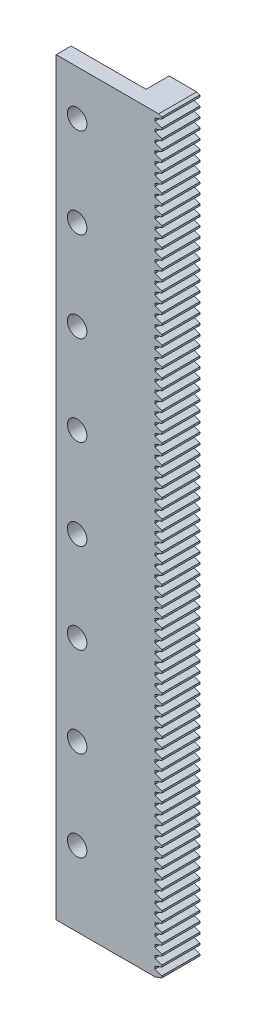
SolidWorks part; units mm, degrees
ref_plane "Front Plane" through (0, 0, 0) normal (0, 0, 1) x (1, 0, 0)
ref_plane "Top Plane" through (0, 0, 0) normal (0, 1, 0) x (1, 0, 0)
ref_plane "Right Plane" through (0, 0, 0) normal (1, 0, 0) x (0, 0, -1)
sketch "Sketch2" plane through (0, 0, 0) normal (0, 0, 1) x (1, 0, 0)
  line L0 (0, -62.5) -> (0, 62.5) construction
  line L1 (-3.5, -62.5) -> (3.5, -62.5) construction
  line L2 (-3.5, -62.5) -> (-3.5, 62.5) construction
  line L3 (-3.5, 62.5) -> (3.5, 62.5) construction
  line L4 (3.5, -62.5) -> (3.5, 62.5) construction
  line L5 (-3.5, -62.5) -> (3.5, 62.5) construction
  line L6 (-3.5, 62.5) -> (3.5, -62.5) construction
  line L202 (3.5, -62.5) -> (-3.5, -62.5)
  line L203 (-3.5, -62.5) -> (-3.5, 62.5)
  line L204 (-3.5, 62.5) -> (13.6024, 62.5)
  line L591 (3.5, -62.5) -> (8, -62.5)
  line L592 (-8, -15) -> (8, -15) construction
  line L593 (-8, -15) -> (-8, 15) construction
  line L594 (-8, 15) -> (8, 15) construction
  line L595 (8, -15) -> (8, 15) construction
  line L596 (-8, -15) -> (8, 15) construction
  line L597 (-8, 15) -> (8, -15) construction
  line L598 (8, -62.5) -> (13, -62.5)
  line L600 (13, -62.5) -> (14.125, -62.0905)
  line L601 (14.125, -62.0905) -> (14.125, -61.7831)
  line L602 (14.125, -61.7831) -> (13, -61.3736)
  line L603 (13, -61.3736) -> (13, -60.9292)
  line L604 (13, -60.9292) -> (14.125, -60.5197)
  line L605 (14.125, -60.5197) -> (14.125, -60.2123)
  line L606 (14.125, -60.2123) -> (13, -59.8028)
  line L607 (13, -59.8028) -> (13, -59.3584)
  line L608 (13, -59.3584) -> (14.125, -58.9489)
  line L609 (14.125, -58.9489) -> (14.125, -58.6415)
  line L610 (14.125, -58.6415) -> (13, -58.232)
  line L611 (13, -58.232) -> (13, -57.7876)
  line L612 (13, -57.7876) -> (14.125, -57.3781)
  line L613 (14.125, -57.3781) -> (14.125, -57.0707)
  line L614 (14.125, -57.0707) -> (13, -56.6613)
  line L615 (13, -56.6613) -> (13, -56.2168)
  line L616 (13, -56.2168) -> (14.125, -55.8073)
  line L617 (14.125, -55.8073) -> (14.125, -55.4999)
  line L618 (14.125, -55.4999) -> (13, -55.0905)
  line L619 (13, -55.0905) -> (13, -54.646)
  line L620 (13, -54.646) -> (14.125, -54.2366)
  line L621 (14.125, -54.2366) -> (14.125, -53.9291)
  line L622 (14.125, -53.9291) -> (13, -53.5197)
  line L623 (13, -53.5197) -> (13, -53.0752)
  line L624 (13, -53.0752) -> (14.125, -52.6658)
  line L625 (14.125, -52.6658) -> (14.125, -52.3583)
  line L626 (14.125, -52.3583) -> (13, -51.9489)
  line L627 (13, -51.9489) -> (13, -51.5044)
  line L628 (13, -51.5044) -> (14.125, -51.095)
  line L629 (14.125, -51.095) -> (14.125, -50.7875)
  line L630 (14.125, -50.7875) -> (13, -50.3781)
  line L631 (13, -50.3781) -> (13, -49.9336)
  line L632 (13, -49.9336) -> (14.125, -49.5242)
  line L633 (14.125, -49.5242) -> (14.125, -49.2167)
  line L634 (14.125, -49.2167) -> (13, -48.8073)
  line L635 (13, -48.8073) -> (13, -48.3628)
  line L636 (13, -48.3628) -> (14.125, -47.9534)
  line L637 (14.125, -47.9534) -> (14.125, -47.6459)
  line L638 (14.125, -47.6459) -> (13, -47.2365)
  line L639 (13, -47.2365) -> (13, -46.792)
  line L640 (13, -46.792) -> (14.125, -46.3826)
  line L641 (14.125, -46.3826) -> (14.125, -46.0751)
  line L642 (14.125, -46.0751) -> (13, -45.6657)
  line L643 (13, -45.6657) -> (13, -45.2212)
  line L644 (13, -45.2212) -> (14.125, -44.8118)
  line L645 (14.125, -44.8118) -> (14.125, -44.5043)
  line L646 (14.125, -44.5043) -> (13, -44.0949)
  line L647 (13, -44.0949) -> (13, -43.6504)
  line L648 (13, -43.6504) -> (14.125, -43.241)
  line L649 (14.125, -43.241) -> (14.125, -42.9335)
  line L650 (14.125, -42.9335) -> (13, -42.5241)
  line L651 (13, -42.5241) -> (13, -42.0796)
  line L652 (13, -42.0796) -> (14.125, -41.6702)
  line L653 (14.125, -41.6702) -> (14.125, -41.3628)
  line L654 (14.125, -41.3628) -> (13, -40.9533)
  line L655 (13, -40.9533) -> (13, -40.5089)
  line L656 (13, -40.5089) -> (14.125, -40.0994)
  line L657 (14.125, -40.0994) -> (14.125, -39.792)
  line L658 (14.125, -39.792) -> (13, -39.3825)
  line L659 (13, -39.3825) -> (13, -38.9381)
  line L660 (13, -38.9381) -> (14.125, -38.5286)
  line L661 (14.125, -38.5286) -> (14.125, -38.2212)
  line L662 (14.125, -38.2212) -> (13, -37.8117)
  line L663 (13, -37.8117) -> (13, -37.3673)
  line L664 (13, -37.3673) -> (14.125, -36.9578)
  line L665 (14.125, -36.9578) -> (14.125, -36.6504)
  line L666 (14.125, -36.6504) -> (13, -36.2409)
  line L667 (13, -36.2409) -> (13, -35.7965)
  line L668 (13, -35.7965) -> (14.125, -35.387)
  line L669 (14.125, -35.387) -> (14.125, -35.0796)
  line L670 (14.125, -35.0796) -> (13, -34.6701)
  line L671 (13, -34.6701) -> (13, -34.2257)
  line L672 (13, -34.2257) -> (14.125, -33.8162)
  line L673 (14.125, -33.8162) -> (14.125, -33.5088)
  line L674 (14.125, -33.5088) -> (13, -33.0993)
  line L675 (13, -33.0993) -> (13, -32.6549)
  line L676 (13, -32.6549) -> (14.125, -32.2454)
  line L677 (14.125, -32.2454) -> (14.125, -31.938)
  line L678 (14.125, -31.938) -> (13, -31.5285)
  line L679 (13, -31.5285) -> (13, -31.0841)
  line L680 (13, -31.0841) -> (14.125, -30.6746)
  line L681 (14.125, -30.6746) -> (14.125, -30.3672)
  line L682 (14.125, -30.3672) -> (13, -29.9577)
  line L683 (13, -29.9577) -> (13, -29.5133)
  line L684 (13, -29.5133) -> (14.125, -29.1038)
  line L685 (14.125, -29.1038) -> (14.125, -28.7964)
  line L686 (14.125, -28.7964) -> (13, -28.3869)
  line L687 (13, -28.3869) -> (13, -27.9425)
  line L688 (13, -27.9425) -> (14.125, -27.533)
  line L689 (14.125, -27.533) -> (14.125, -27.2256)
  line L690 (14.125, -27.2256) -> (13, -26.8161)
  line L691 (13, -26.8161) -> (13, -26.3717)
  line L692 (13, -26.3717) -> (14.125, -25.9622)
  line L693 (14.125, -25.9622) -> (14.125, -25.6548)
  line L694 (14.125, -25.6548) -> (13, -25.2453)
  line L695 (13, -25.2453) -> (13, -24.8009)
  line L696 (13, -24.8009) -> (14.125, -24.3914)
  line L697 (14.125, -24.3914) -> (14.125, -24.084)
  line L698 (14.125, -24.084) -> (13, -23.6745)
  line L699 (13, -23.6745) -> (13, -23.2301)
  line L700 (13, -23.2301) -> (14.125, -22.8206)
  line L701 (14.125, -22.8206) -> (14.125, -22.5132)
  line L702 (14.125, -22.5132) -> (13, -22.1037)
  line L703 (13, -22.1037) -> (13, -21.6593)
  line L704 (13, -21.6593) -> (14.125, -21.2498)
  line L705 (14.125, -21.2498) -> (14.125, -20.9424)
  line L706 (14.125, -20.9424) -> (13, -20.5329)
  line L707 (13, -20.5329) -> (13, -20.0885)
  line L708 (13, -20.0885) -> (14.125, -19.679)
  line L709 (14.125, -19.679) -> (14.125, -19.3716)
  line L710 (14.125, -19.3716) -> (13, -18.9621)
  line L711 (13, -18.9621) -> (13, -18.5177)
  line L712 (13, -18.5177) -> (14.125, -18.1082)
  line L713 (14.125, -18.1082) -> (14.125, -17.8008)
  line L714 (14.125, -17.8008) -> (13, -17.3913)
  line L715 (13, -17.3913) -> (13, -16.9469)
  line L716 (13, -16.9469) -> (14.125, -16.5374)
  line L717 (14.125, -16.5374) -> (14.125, -16.23)
  line L718 (14.125, -16.23) -> (13, -15.8205)
  line L719 (13, -15.8205) -> (13, -15.3761)
  line L720 (13, -15.3761) -> (14.125, -14.9666)
  line L721 (14.125, -14.9666) -> (14.125, -14.6592)
  line L722 (14.125, -14.6592) -> (13, -14.2497)
  line L723 (13, -14.2497) -> (13, -13.8053)
  line L724 (13, -13.8053) -> (14.125, -13.3958)
  line L725 (14.125, -13.3958) -> (14.125, -13.0884)
  line L726 (14.125, -13.0884) -> (13, -12.679)
  line L727 (13, -12.679) -> (13, -12.2345)
  line L728 (13, -12.2345) -> (14.125, -11.8251)
  line L729 (14.125, -11.8251) -> (14.125, -11.5176)
  line L730 (14.125, -11.5176) -> (13, -11.1082)
  line L731 (13, -11.1082) -> (13, -10.6637)
  line L732 (13, -10.6637) -> (14.125, -10.2543)
  line L733 (14.125, -10.2543) -> (14.125, -9.9468)
  line L734 (14.125, -9.9468) -> (13, -9.5374)
  line L735 (13, -9.5374) -> (13, -9.0929)
  line L736 (13, -9.0929) -> (14.125, -8.6835)
  line L737 (14.125, -8.6835) -> (14.125, -8.376)
  line L738 (14.125, -8.376) -> (13, -7.9666)
  line L739 (13, -7.9666) -> (13, -7.5221)
  line L740 (13, -7.5221) -> (14.125, -7.1127)
  line L741 (14.125, -7.1127) -> (14.125, -6.8052)
  line L742 (14.125, -6.8052) -> (13, -6.3958)
  line L743 (13, -6.3958) -> (13, -5.9513)
  line L744 (13, -5.9513) -> (14.125, -5.5419)
  line L745 (14.125, -5.5419) -> (14.125, -5.2344)
  line L746 (14.125, -5.2344) -> (13, -4.825)
  line L747 (13, -4.825) -> (13, -4.3805)
  line L748 (13, -4.3805) -> (14.125, -3.9711)
  line L749 (14.125, -3.9711) -> (14.125, -3.6636)
  line L750 (14.125, -3.6636) -> (13, -3.2542)
  line L751 (13, -3.2542) -> (13, -2.8097)
  line L752 (13, -2.8097) -> (14.125, -2.4003)
  line L753 (14.125, -2.4003) -> (14.125, -2.0928)
  line L754 (14.125, -2.0928) -> (13, -1.6834)
  line L755 (13, -1.6834) -> (13, -1.2389)
  line L756 (13, -1.2389) -> (14.125, -0.8295)
  line L757 (14.125, -0.8295) -> (14.125, -0.522)
  line L758 (14.125, -0.522) -> (13, -0.1126)
  line L759 (13, -0.1126) -> (13, 0.3319)
  line L760 (13, 0.3319) -> (14.125, 0.7413)
  line L761 (14.125, 0.7413) -> (14.125, 1.0487)
  line L762 (14.125, 1.0487) -> (13, 1.4582)
  line L763 (13, 1.4582) -> (13, 1.9026)
  line L764 (13, 1.9026) -> (14.125, 2.3121)
  line L765 (14.125, 2.3121) -> (14.125, 2.6195)
  line L766 (14.125, 2.6195) -> (13, 3.029)
  line L767 (13, 3.029) -> (13, 3.4734)
  line L768 (13, 3.4734) -> (14.125, 3.8829)
  line L769 (14.125, 3.8829) -> (14.125, 4.1903)
  line L770 (14.125, 4.1903) -> (13, 4.5998)
  line L771 (13, 4.5998) -> (13, 5.0442)
  line L772 (13, 5.0442) -> (14.125, 5.4537)
  line L773 (14.125, 5.4537) -> (14.125, 5.7611)
  line L774 (14.125, 5.7611) -> (13, 6.1706)
  line L775 (13, 6.1706) -> (13, 6.615)
  line L776 (13, 6.615) -> (14.125, 7.0245)
  line L777 (14.125, 7.0245) -> (14.125, 7.3319)
  line L778 (14.125, 7.3319) -> (13, 7.7414)
  line L779 (13, 7.7414) -> (13, 8.1858)
  line L780 (13, 8.1858) -> (14.125, 8.5953)
  line L781 (14.125, 8.5953) -> (14.125, 8.9027)
  line L782 (14.125, 8.9027) -> (13, 9.3122)
  line L783 (13, 9.3122) -> (13, 9.7566)
  line L784 (13, 9.7566) -> (14.125, 10.1661)
  line L785 (14.125, 10.1661) -> (14.125, 10.4735)
  line L786 (14.125, 10.4735) -> (13, 10.883)
  line L787 (13, 10.883) -> (13, 11.3274)
  line L788 (13, 11.3274) -> (14.125, 11.7369)
  line L789 (14.125, 11.7369) -> (14.125, 12.0443)
  line L790 (14.125, 12.0443) -> (13, 12.4538)
  line L791 (13, 12.4538) -> (13, 12.8982)
  line L792 (13, 12.8982) -> (14.125, 13.3077)
  line L793 (14.125, 13.3077) -> (14.125, 13.6151)
  line L794 (14.125, 13.6151) -> (13, 14.0246)
  line L795 (13, 14.0246) -> (13, 14.469)
  line L796 (13, 14.469) -> (14.125, 14.8785)
  line L797 (14.125, 14.8785) -> (14.125, 15.1859)
  line L798 (14.125, 15.1859) -> (13, 15.5954)
  line L799 (13, 15.5954) -> (13, 16.0398)
  line L800 (13, 16.0398) -> (14.125, 16.4493)
  line L801 (14.125, 16.4493) -> (14.125, 16.7567)
  line L802 (14.125, 16.7567) -> (13, 17.1662)
  line L803 (13, 17.1662) -> (13, 17.6106)
  line L804 (13, 17.6106) -> (14.125, 18.0201)
  line L805 (14.125, 18.0201) -> (14.125, 18.3275)
  line L806 (14.125, 18.3275) -> (13, 18.737)
  line L807 (13, 18.737) -> (13, 19.1814)
  line L808 (13, 19.1814) -> (14.125, 19.5909)
  line L809 (14.125, 19.5909) -> (14.125, 19.8983)
  line L810 (14.125, 19.8983) -> (13, 20.3078)
  line L811 (13, 20.3078) -> (13, 20.7522)
  line L812 (13, 20.7522) -> (14.125, 21.1617)
  line L813 (14.125, 21.1617) -> (14.125, 21.4691)
  line L814 (14.125, 21.4691) -> (13, 21.8786)
  line L815 (13, 21.8786) -> (13, 22.323)
  line L816 (13, 22.323) -> (14.125, 22.7325)
  line L817 (14.125, 22.7325) -> (14.125, 23.0399)
  line L818 (14.125, 23.0399) -> (13, 23.4494)
  line L819 (13, 23.4494) -> (13, 23.8938)
  line L820 (13, 23.8938) -> (14.125, 24.3033)
  line L821 (14.125, 24.3033) -> (14.125, 24.6107)
  line L822 (14.125, 24.6107) -> (13, 25.0202)
  line L823 (13, 25.0202) -> (13, 25.4646)
  line L824 (13, 25.4646) -> (14.125, 25.8741)
  line L825 (14.125, 25.8741) -> (14.125, 26.1815)
  line L826 (14.125, 26.1815) -> (13, 26.591)
  line L827 (13, 26.591) -> (13, 27.0354)
  line L828 (13, 27.0354) -> (14.125, 27.4449)
  line L829 (14.125, 27.4449) -> (14.125, 27.7523)
  line L830 (14.125, 27.7523) -> (13, 28.1618)
  line L831 (13, 28.1618) -> (13, 28.6062)
  line L832 (13, 28.6062) -> (14.125, 29.0157)
  line L833 (14.125, 29.0157) -> (14.125, 29.3231)
  line L834 (14.125, 29.3231) -> (13, 29.7325)
  line L835 (13, 29.7325) -> (13, 30.177)
  line L836 (13, 30.177) -> (14.125, 30.5864)
  line L837 (14.125, 30.5864) -> (14.125, 30.8939)
  line L838 (14.125, 30.8939) -> (13, 31.3033)
  line L839 (13, 31.3033) -> (13, 31.7478)
  line L840 (13, 31.7478) -> (14.125, 32.1572)
  line L841 (14.125, 32.1572) -> (14.125, 32.4647)
  line L842 (14.125, 32.4647) -> (13, 32.8741)
  line L843 (13, 32.8741) -> (13, 33.3186)
  line L844 (13, 33.3186) -> (14.125, 33.728)
  line L845 (14.125, 33.728) -> (14.125, 34.0355)
  line L846 (14.125, 34.0355) -> (13, 34.4449)
  line L847 (13, 34.4449) -> (13, 34.8894)
  line L848 (13, 34.8894) -> (14.125, 35.2988)
  line L849 (14.125, 35.2988) -> (14.125, 35.6063)
  line L850 (14.125, 35.6063) -> (13, 36.0157)
  line L851 (13, 36.0157) -> (13, 36.4602)
  line L852 (13, 36.4602) -> (14.125, 36.8696)
  line L853 (14.125, 36.8696) -> (14.125, 37.1771)
  line L854 (14.125, 37.1771) -> (13, 37.5865)
  line L855 (13, 37.5865) -> (13, 38.031)
  line L856 (13, 38.031) -> (14.125, 38.4404)
  line L857 (14.125, 38.4404) -> (14.125, 38.7479)
  line L858 (14.125, 38.7479) -> (13, 39.1573)
  line L859 (13, 39.1573) -> (13, 39.6018)
  line L860 (13, 39.6018) -> (14.125, 40.0112)
  line L861 (14.125, 40.0112) -> (14.125, 40.3187)
  line L862 (14.125, 40.3187) -> (13, 40.7281)
  line L863 (13, 40.7281) -> (13, 41.1726)
  line L864 (13, 41.1726) -> (14.125, 41.582)
  line L865 (14.125, 41.582) -> (14.125, 41.8895)
  line L866 (14.125, 41.8895) -> (13, 42.2989)
  line L867 (13, 42.2989) -> (13, 42.7434)
  line L868 (13, 42.7434) -> (14.125, 43.1528)
  line L869 (14.125, 43.1528) -> (14.125, 43.4602)
  line L870 (14.125, 43.4602) -> (13, 43.8697)
  line L871 (13, 43.8697) -> (13, 44.3142)
  line L872 (13, 44.3142) -> (14.125, 44.7236)
  line L873 (14.125, 44.7236) -> (14.125, 45.031)
  line L874 (14.125, 45.031) -> (13, 45.4405)
  line L875 (13, 45.4405) -> (13, 45.8849)
  line L876 (13, 45.8849) -> (14.125, 46.2944)
  line L877 (14.125, 46.2944) -> (14.125, 46.6018)
  line L878 (14.125, 46.6018) -> (13, 47.0113)
  line L879 (13, 47.0113) -> (13, 47.4557)
  line L880 (13, 47.4557) -> (14.125, 47.8652)
  line L881 (14.125, 47.8652) -> (14.125, 48.1726)
  line L882 (14.125, 48.1726) -> (13, 48.5821)
  line L883 (13, 48.5821) -> (13, 49.0265)
  line L884 (13, 49.0265) -> (14.125, 49.436)
  line L885 (14.125, 49.436) -> (14.125, 49.7434)
  line L886 (14.125, 49.7434) -> (13, 50.1529)
  line L887 (13, 50.1529) -> (13, 50.5973)
  line L888 (13, 50.5973) -> (14.125, 51.0068)
  line L889 (14.125, 51.0068) -> (14.125, 51.3142)
  line L890 (14.125, 51.3142) -> (13, 51.7237)
  line L891 (13, 51.7237) -> (13, 52.1681)
  line L892 (13, 52.1681) -> (14.125, 52.5776)
  line L893 (14.125, 52.5776) -> (14.125, 52.885)
  line L894 (14.125, 52.885) -> (13, 53.2945)
  line L895 (13, 53.2945) -> (13, 53.7389)
  line L896 (13, 53.7389) -> (14.125, 54.1484)
  line L897 (14.125, 54.1484) -> (14.125, 54.4558)
  line L898 (14.125, 54.4558) -> (13, 54.8653)
  line L899 (13, 54.8653) -> (13, 55.3097)
  line L900 (13, 55.3097) -> (14.125, 55.7192)
  line L901 (14.125, 55.7192) -> (14.125, 56.0266)
  line L902 (14.125, 56.0266) -> (13, 56.4361)
  line L903 (13, 56.4361) -> (13, 56.8805)
  line L904 (13, 56.8805) -> (14.125, 57.29)
  line L905 (14.125, 57.29) -> (14.125, 57.5974)
  line L906 (14.125, 57.5974) -> (13, 58.0069)
  line L907 (13, 58.0069) -> (13, 58.4513)
  line L908 (13, 58.4513) -> (14.125, 58.8608)
  line L909 (14.125, 58.8608) -> (14.125, 59.1682)
  line L910 (14.125, 59.1682) -> (13, 59.5777)
  line L911 (13, 59.5777) -> (13, 60.0221)
  line L912 (13, 60.0221) -> (14.125, 60.4316)
  line L913 (14.125, 60.4316) -> (14.125, 60.739)
  line L914 (14.125, 60.739) -> (13, 61.1485)
  line L915 (13, 61.1485) -> (13, 61.5929)
  line L916 (13, 61.5929) -> (14.125, 62.0024)
  line L917 (14.125, 62.0024) -> (14.125, 62.3098)
  line L918 (14.125, 62.3098) -> (13, 62.7193)
  line L919 (13, 62.7193) -> (13, 63.1637)
  line L920 (13, 63.1637) -> (14.125, 63.5732)
  line L921 (14.125, 63.5732) -> (14.125, 63.8806)
  line L922 (14.125, 63.8806) -> (13, 64.2901)
  line L923 (13, 64.2901) -> (13, 64.7345)
  line L924 (13, 64.7345) -> (14.125, 65.144)
  line L925 (14.125, 65.144) -> (14.125, 65.4514)
  line L926 (14.125, 65.4514) -> (13, 65.8609)
  line L927 (13, 65.8609) -> (13, 66.3053)
  line L928 (13, 66.3053) -> (14.125, 66.7148)
  line L929 (14.125, 66.7148) -> (14.125, 67.0222)
  line L930 (14.125, 67.0222) -> (13, 67.4317)
  line L931 (13, 67.4317) -> (13, 67.8761)
  line L932 (13, 67.8761) -> (14.125, 68.2856)
  line L933 (14.125, 68.2856) -> (14.125, 68.593)
  line L934 (14.125, 68.593) -> (13, 69.0025)
  line L935 (13, 69.0025) -> (13, 69.4469)
  line L936 (13, 69.4469) -> (14.125, 69.8564)
  line L937 (14.125, 69.8564) -> (14.125, 70.1638)
  line L938 (14.125, 70.1638) -> (13, 70.5733)
  line L939 (13, 70.5733) -> (13, 71.0177)
  line L940 (13, 71.0177) -> (14.125, 71.4272)
  line L941 (14.125, 71.4272) -> (14.125, 71.7346)
  line L942 (14.125, 71.7346) -> (13, 72.144)
  line L943 (13, 72.144) -> (13, 72.5885)
  line L944 (13, 72.5885) -> (14.125, 72.998)
  line L945 (14.125, 72.998) -> (14.125, 73.3054)
  line L946 (14.125, 73.3054) -> (13, 73.7148)
  line L947 (13, 73.7148) -> (13, 74.1593)
  line L948 (13, 74.1593) -> (14.125, 74.5687)
  line L949 (14.125, 74.5687) -> (14.125, 74.8762)
  line L950 (14.125, 74.8762) -> (13, 75.2856)
  line L951 (13, 75.2856) -> (13, 75.7301)
  line L952 (13, 75.7301) -> (14.125, 76.1395)
  line L953 (14.125, 76.1395) -> (14.125, 76.447)
  line L954 (14.125, 76.447) -> (13, 76.8564)
  line L955 (13, 76.8564) -> (13, 77.3009)
  line L956 (13, 77.3009) -> (14.125, 77.7103)
  line L957 (14.125, 77.7103) -> (14.125, 78.0178)
  line L958 (14.125, 78.0178) -> (13, 78.4272)
  line L959 (13, 78.4272) -> (13, 78.8717)
  line L960 (13, 78.8717) -> (14.125, 79.2811)
  line L961 (14.125, 79.2811) -> (14.125, 79.5886)
  line L962 (14.125, 79.5886) -> (13, 79.998)
  line L963 (13, 79.998) -> (13, 80.4425)
  line L964 (13, 80.4425) -> (14.125, 80.8519)
  line L965 (14.125, 80.8519) -> (14.125, 81.1594)
  line L966 (14.125, 81.1594) -> (13, 81.5688)
  line L967 (13, 81.5688) -> (13, 82.0133)
  line L968 (13, 82.0133) -> (14.125, 82.4227)
  line L969 (14.125, 82.4227) -> (14.125, 82.7302)
  line L970 (14.125, 82.7302) -> (13, 83.1396)
  line L971 (13, 83.1396) -> (13, 83.5841)
  line L972 (13, 83.5841) -> (14.125, 83.9935)
  line L973 (14.125, 83.9935) -> (14.125, 84.301)
  line L974 (14.125, 84.301) -> (13, 84.7104)
  line L975 (13, 84.7104) -> (13, 85.1549)
  line L976 (13, 85.1549) -> (14.125, 85.5643)
  line L977 (14.125, 85.5643) -> (14.125, 85.8717)
  line L978 (14.125, 85.8717) -> (13, 86.2812)
  line L979 (13, 86.2812) -> (13, 86.7257)
  line L980 (13, 86.7257) -> (14.125, 87.1351)
  line L981 (14.125, 87.1351) -> (14.125, 87.4425)
  line L982 (14.125, 87.4425) -> (13, 87.852)
  line L983 (13, 87.852) -> (13, 88.2964)
  line L984 (13, 88.2964) -> (14.125, 88.7059)
  line L985 (14.125, 88.7059) -> (14.125, 89.0133)
  line L986 (14.125, 89.0133) -> (13, 89.4228)
  line L987 (13, 89.4228) -> (13, 89.8672)
  line L988 (13, 89.8672) -> (14.125, 90.2767)
  line L989 (14.125, 90.2767) -> (14.125, 90.5841)
  line L990 (14.125, 90.5841) -> (13, 90.9936)
  line L991 (13, 90.9936) -> (13, 91.438)
  line L992 (13, 91.438) -> (14.125, 91.8475)
  line L993 (14.125, 91.8475) -> (14.125, 92.1549)
  line L994 (14.125, 92.1549) -> (13, 92.5644)
  line L995 (13, 92.5644) -> (13, 93.0088)
  line L996 (13, 93.0088) -> (14.125, 93.4183)
  line L997 (14.125, 93.4183) -> (14.125, 93.7257)
  line L998 (14.125, 93.7257) -> (13, 94.1352)
  line L999 (13, 94.1352) -> (13, 94.5796)
  line L1000 (13, 94.5796) -> (14.125, 94.9891)
  line L1001 (14.125, 94.9891) -> (14.125, 95.2965)
  line L1002 (14.125, 95.2965) -> (13, 95.706)
  line L1003 (13, 95.706) -> (13, 96.1504)
  line L1004 (13, 96.1504) -> (14.125, 96.5599)
  line L1005 (14.125, 96.5599) -> (14.125, 96.8673)
  line L1006 (14.125, 96.8673) -> (13, 97.2768)
  line L1007 (13, 97.2768) -> (13, 97.7212)
  line L1008 (13, 97.7212) -> (14.125, 98.1307)
  line L1009 (14.125, 98.1307) -> (14.125, 98.4381)
  line L1010 (14.125, 98.4381) -> (13, 98.8476)
  line L1011 (13, 98.8476) -> (13, 99.292)
  line L1012 (13, 99.292) -> (14.125, 99.7015)
  line L1013 (14.125, 99.7015) -> (14.125, 100.0089)
  line L1014 (14.125, 100.0089) -> (13, 100.4184)
  line L1015 (13, 100.4184) -> (13, 100.8628)
  line L1016 (13, 100.8628) -> (14.125, 101.2723)
  line L1017 (14.125, 101.2723) -> (14.125, 101.5797)
  line L1018 (14.125, 101.5797) -> (13, 101.9892)
  line L1019 (13, 101.9892) -> (13, 102.4336)
  line L1020 (13, 102.4336) -> (14.125, 102.8431)
  line L1021 (14.125, 102.8431) -> (14.125, 103.1505)
  line L1022 (14.125, 103.1505) -> (13, 103.56)
  line L1023 (13, 103.56) -> (13, 104.0044)
  line L1024 (13, 104.0044) -> (14.125, 104.4139)
  line L1025 (14.125, 104.4139) -> (14.125, 104.7213)
  line L1026 (14.125, 104.7213) -> (13, 105.1308)
  line L1027 (13, 105.1308) -> (13, 105.5752)
  line L1028 (13, 105.5752) -> (14.125, 105.9847)
  line L1029 (14.125, 105.9847) -> (14.125, 106.2921)
  line L1030 (14.125, 106.2921) -> (13, 106.7016)
  line L1031 (13, 106.7016) -> (13, 107.146)
  line L1032 (13, 107.146) -> (14.125, 107.5555)
  line L1033 (14.125, 107.5555) -> (14.125, 107.8629)
  line L1034 (14.125, 107.8629) -> (13, 108.2724)
  line L1035 (13, 108.2724) -> (13, 108.7168)
  line L1036 (13, 108.7168) -> (14.125, 109.1263)
  line L1037 (14.125, 109.1263) -> (14.125, 109.4337)
  line L1038 (14.125, 109.4337) -> (13, 109.8432)
  line L1039 (13, 109.8432) -> (13, 110.2876)
  line L1040 (13, 110.2876) -> (14.125, 110.6971)
  line L1041 (14.125, 110.6971) -> (14.125, 111.0045)
  line L1042 (14.125, 111.0045) -> (13, 111.414)
  line L1043 (13, 111.414) -> (13, 111.8584)
  line L1044 (13, 111.8584) -> (14.125, 112.2679)
  line L1045 (14.125, 112.2679) -> (14.125, 112.5753)
  line L1046 (14.125, 112.5753) -> (13, 112.9848)
  line L1047 (13, 112.9848) -> (13, 113.4292)
  line L1048 (13, 113.4292) -> (14.125, 113.8387)
  line L1049 (14.125, 113.8387) -> (14.125, 114.1461)
  line L1050 (14.125, 114.1461) -> (13, 114.5555)
  line L1051 (13, 114.5555) -> (13, 115)
  line L1052 (13, 115) -> (14.125, 115.4095)
  line L1053 (14.125, 115.4095) -> (14.125, 115.7169)
  line L1054 (14.125, 115.7169) -> (13, 116.1263)
  line L1055 (13, 116.1263) -> (13, 116.5708)
  line L1056 (13, 116.5708) -> (14.125, 116.9802)
  line L1057 (14.125, 116.9802) -> (14.125, 117.2877)
  line L1058 (14.125, 117.2877) -> (13, 117.6971)
  line L1059 (13, 117.6971) -> (13, 118.1416)
  line L1060 (13, 118.1416) -> (14.125, 118.551)
  line L1061 (14.125, 118.551) -> (14.125, 118.8585)
  line L1062 (14.125, 118.8585) -> (13, 119.2679)
  line L1063 (13, 119.2679) -> (13, 119.7124)
  line L1064 (13, 119.7124) -> (14.125, 120.1218)
  line L1065 (14.125, 120.1218) -> (14.125, 120.4293)
  line L1066 (14.125, 120.4293) -> (13, 120.8387)
  line L1067 (13, 120.8387) -> (13, 121.2832)
  line L1068 (13, 121.2832) -> (14.125, 121.6926)
  line L1069 (14.125, 121.6926) -> (14.125, 122.0001)
  line L1070 (14.125, 122.0001) -> (13, 122.4095)
  line L1071 (13, 122.4095) -> (13, 122.854)
  line L1072 (13, 122.854) -> (14.125, 123.2634)
  line L1073 (14.125, 123.2634) -> (14.125, 123.5709)
  line L1074 (14.125, 123.5709) -> (13, 123.9803)
  line L1075 (13, 123.9803) -> (13, 124.4248)
  line L1076 (13, 124.4248) -> (14.125, 124.8342)
  line L1077 (14.125, 124.8342) -> (14.125, 125.1417)
  line L1078 (14.125, 125.1417) -> (13, 125.5511)
  line L1079 (13, 125.5511) -> (13, 125.9956)
  line L1080 (13, 125.9956) -> (14.125, 126.405)
  line L1081 (14.125, 126.405) -> (14.125, 126.7125)
  line L1082 (14.125, 126.7125) -> (13, 127.1219)
  line L1083 (13, 127.1219) -> (13, 127.5664)
  line L1084 (13, 127.5664) -> (14.125, 127.9758)
  line L1085 (14.125, 127.9758) -> (14.125, 128.2832)
  line L1086 (14.125, 128.2832) -> (13, 128.6927)
  line L1087 (13, 128.6927) -> (13, 129.1372)
  line L1088 (13, 129.1372) -> (14.125, 129.5466)
  line L1089 (14.125, 129.5466) -> (14.125, 129.854)
  line L1090 (14.125, 129.854) -> (13, 130.2635)
  line L1091 (13, 130.2635) -> (13, 130.7079)
  line L1092 (13, 130.7079) -> (14.125, 131.1174)
  line L1093 (14.125, 131.1174) -> (14.125, 131.4248)
  line L1094 (14.125, 131.4248) -> (13, 131.8343)
  line L1095 (13, 131.8343) -> (13, 132.2787)
  line L1096 (13, 132.2787) -> (14.125, 132.6882)
  line L1097 (14.125, 132.6882) -> (14.125, 132.9956)
  line L1098 (14.125, 132.9956) -> (13, 133.4051)
  line L1099 (13, 133.4051) -> (13, 133.8495)
  line L1100 (13, 133.8495) -> (14.125, 134.259)
  line L1101 (14.125, 134.259) -> (14.125, 134.5664)
  line L1102 (14.125, 134.5664) -> (13, 134.9759)
  line L1103 (13, 134.9759) -> (13, 135.4203)
  line L1104 (13, 135.4203) -> (14.125, 135.8298)
  line L1105 (14.125, 135.8298) -> (14.125, 136.1372)
  line L1106 (14.125, 136.1372) -> (13, 136.5467)
  line L1107 (13, 136.5467) -> (13, 136.9911)
  line L1108 (13, 136.9911) -> (14.125, 137.4006)
  line L1109 (14.125, 137.4006) -> (14.125, 137.708)
  line L1110 (14.125, 137.708) -> (13, 138.1175)
  line L1111 (13, 138.1175) -> (13, 138.5619)
  line L1112 (13, 138.5619) -> (14.125, 138.9714)
  line L1113 (14.125, 138.9714) -> (14.125, 139.2788)
  line L1114 (14.125, 139.2788) -> (13, 139.6883)
  line L1115 (13, 139.6883) -> (13, 140.1327)
  line L1116 (13, 140.1327) -> (14.125, 140.5422)
  line L1117 (14.125, 140.5422) -> (14.125, 140.8496)
  line L1118 (14.125, 140.8496) -> (13, 141.2591)
  line L1119 (13, 141.2591) -> (13, 141.7035)
  line L1120 (13, 141.7035) -> (14.125, 142.113)
  line L1121 (14.125, 142.113) -> (14.125, 142.4204)
  line L1122 (14.125, 142.4204) -> (13, 142.8299)
  line L1123 (13, 142.8299) -> (13, 143.2743)
  line L1124 (13, 143.2743) -> (14.125, 143.6838)
  line L1125 (14.125, 143.6838) -> (14.125, 143.9912)
  line L1126 (14.125, 143.9912) -> (13, 144.4007)
  line L1127 (13, 144.4007) -> (13, 144.8451)
  line L1128 (13, 144.8451) -> (14.125, 145.2546)
  line L1129 (14.125, 145.2546) -> (14.125, 145.562)
  line L1130 (14.125, 145.562) -> (13, 145.9715)
  line L1131 (13, 145.9715) -> (13, 146.4159)
  line L1132 (13, 146.4159) -> (14.125, 146.8254)
  line L1133 (14.125, 146.8254) -> (14.125, 147.1328)
  line L1134 (14.125, 147.1328) -> (13, 147.5423)
  line L1135 (13, 147.5423) -> (13, 147.9867)
  line L1136 (13, 147.9867) -> (14.125, 148.3962)
  line L1137 (14.125, 148.3962) -> (14.125, 148.7036)
  line L1138 (14.125, 148.7036) -> (13, 149.1131)
  line L1139 (13, 149.1131) -> (13, 149.5575)
  line L1140 (13, 149.5575) -> (14.125, 149.967)
  line L1141 (14.125, 149.967) -> (14.125, 150.2744)
  line L1142 (14.125, 150.2744) -> (13, 150.6839)
  line L1143 (13, 150.6839) -> (13, 151.1283)
  line L1144 (13, 151.1283) -> (14.125, 151.5378)
  line L1145 (14.125, 151.5378) -> (14.125, 151.8452)
  line L1146 (14.125, 151.8452) -> (13, 152.2547)
  line L1147 (13, 152.2547) -> (13, 152.6991)
  line L1148 (13, 152.6991) -> (14.125, 153.1086)
  line L1149 (14.125, 153.1086) -> (14.125, 153.416)
  line L1150 (14.125, 153.416) -> (13, 153.8255)
  line L1151 (13, 153.8255) -> (13, 154.2699)
  line L1152 (13, 154.2699) -> (14.125, 154.6794)
  line L1153 (14.125, 154.6794) -> (14.125, 154.9868)
  line L1154 (14.125, 154.9868) -> (13, 155.3963)
  line L1155 (13, 155.3963) -> (13, 155.8407)
  line L1156 (13, 155.8407) -> (14.125, 156.2502)
  line L1157 (14.125, 156.2502) -> (14.125, 156.5576)
  line L1158 (14.125, 156.5576) -> (13, 156.9671)
  line L1159 (13, 156.9671) -> (13, 157.4115)
  line L1160 (13, 157.4115) -> (14.125, 157.821)
  line L1161 (14.125, 157.821) -> (14.125, 158.1284)
  line L1162 (14.125, 158.1284) -> (13, 158.5378)
  line L1163 (13, 158.5378) -> (13, 158.9823)
  line L1164 (13, 158.9823) -> (14.125, 159.3917)
  line L1165 (14.125, 159.3917) -> (14.125, 159.6992)
  line L1166 (14.125, 159.6992) -> (13, 160.1086)
  line L1167 (13, 160.1086) -> (13, 160.5531)
  line L1168 (13, 160.5531) -> (14.125, 160.9625)
  line L1169 (14.125, 160.9625) -> (14.125, 161.27)
  line L1170 (14.125, 161.27) -> (13, 161.6794)
  line L1171 (13, 161.6794) -> (13, 162.1239)
  line L1172 (13, 162.1239) -> (14.125, 162.5333)
  line L1173 (14.125, 162.5333) -> (14.125, 162.8408)
  line L1174 (14.125, 162.8408) -> (13, 163.2502)
  line L1175 (13, 163.2502) -> (13, 163.6947)
  line L1176 (13, 163.6947) -> (14.125, 164.1041)
  line L1177 (14.125, 164.1041) -> (14.125, 164.4116)
  line L1178 (14.125, 164.4116) -> (13, 164.821)
  line L1179 (13, 164.821) -> (13, 165.2655)
  line L1180 (13, 165.2655) -> (14.125, 165.6749)
  line L1181 (14.125, 165.6749) -> (14.125, 165.9824)
  line L1182 (14.125, 165.9824) -> (13, 166.3918)
  line L1183 (13, 166.3918) -> (13, 166.8363)
  line L1184 (13, 166.8363) -> (14.125, 167.2457)
  line L1185 (14.125, 167.2457) -> (14.125, 167.5532)
  line L1186 (14.125, 167.5532) -> (13, 167.9626)
  line L1187 (13, 167.9626) -> (13, 168.4071)
  line L1188 (13, 168.4071) -> (14.125, 168.8165)
  line L1189 (14.125, 168.8165) -> (14.125, 169.124)
  line L1190 (14.125, 169.124) -> (13, 169.5334)
  line L1191 (13, 169.5334) -> (13, 169.9779)
  line L1192 (13, 169.9779) -> (14.125, 170.3873)
  line L1193 (14.125, 170.3873) -> (14.125, 170.6948)
  line L1194 (14.125, 170.6948) -> (13, 171.1042)
  line L1195 (13, 171.1042) -> (13, 171.5487)
  line L1196 (13, 171.5487) -> (14.125, 171.9581)
  line L1197 (14.125, 171.9581) -> (14.125, 172.2655)
  line L1198 (14.125, 172.2655) -> (13, 172.675)
  line L1199 (13, 172.675) -> (13, 173.1194)
  line L1200 (13, 173.1194) -> (14.125, 173.5289)
  line L1201 (14.125, 173.5289) -> (14.125, 173.8363)
  line L1202 (14.125, 173.8363) -> (13, 174.2458)
  line L1203 (13, 174.2458) -> (13, 174.6902)
  line L1204 (13, 174.6902) -> (14.125, 175.0997)
  line L1205 (14.125, 175.0997) -> (14.125, 175.4071)
  line L1206 (14.125, 175.4071) -> (13, 175.8166)
  line L1207 (13, 175.8166) -> (13, 176.261)
  line L1208 (13, 176.261) -> (14.125, 176.6705)
  line L1209 (14.125, 176.6705) -> (14.125, 176.9779)
  line L1210 (14.125, 176.9779) -> (13, 177.3874)
  line L1211 (13, 177.3874) -> (13, 177.8318)
  line L1212 (13, 177.8318) -> (14.125, 178.2413)
  line L1213 (14.125, 178.2413) -> (14.125, 178.5487)
  line L1214 (14.125, 178.5487) -> (13, 178.9582)
  line L1215 (13, 178.9582) -> (13, 179.4026)
  line L1216 (13, 179.4026) -> (14.125, 179.8121)
  line L1217 (14.125, 179.8121) -> (14.125, 180.1195)
  line L1218 (14.125, 180.1195) -> (13, 180.529)
  line L1219 (13, 180.529) -> (13, 180.9734)
  line L1220 (13, 180.9734) -> (14.125, 181.3829)
  line L1221 (14.125, 181.3829) -> (14.125, 181.6903)
  line L1222 (14.125, 181.6903) -> (13, 182.0998)
  line L1223 (13, 182.0998) -> (13, 182.5442)
  line L1224 (13, 182.5442) -> (14.125, 182.9537)
  line L1225 (14.125, 182.9537) -> (14.125, 183.2611)
  line L1226 (14.125, 183.2611) -> (13, 183.6706)
  line L1227 (13, 183.6706) -> (13, 184.115)
  line L1228 (13, 184.115) -> (14.125, 184.5245)
  line L1229 (14.125, 184.5245) -> (14.125, 184.8319)
  line L1230 (14.125, 184.8319) -> (13, 185.2414)
  line L1231 (13, 185.2414) -> (13, 185.6858)
  line L1232 (13, 185.6858) -> (14.125, 186.0953)
  line L1233 (14.125, 186.0953) -> (14.125, 186.4027)
  line L1234 (14.125, 186.4027) -> (13, 186.8122)
  line L1235 (13, 186.8122) -> (13, 187.2566)
  line L1236 (13, 187.2566) -> (14.125, 187.6661)
  line L1237 (14.125, 187.6661) -> (14.125, 187.9735)
  line L1238 (14.125, 187.9735) -> (13, 188.383)
  line L1239 (13, 188.383) -> (13, 188.8274)
  line L1240 (13, 188.8274) -> (14.125, 189.2369)
  line L1241 (14.125, 189.2369) -> (14.125, 189.5443)
  line L1242 (14.125, 189.5443) -> (13, 189.9538)
  line L1243 (13, 189.9538) -> (13, 190.3982)
  line L1244 (13, 190.3982) -> (14.125, 190.8077)
  line L1245 (14.125, 190.8077) -> (14.125, 191.1151)
  line L1246 (14.125, 191.1151) -> (13, 191.5246)
  line L1247 (13, 191.5246) -> (13, 191.969)
  line L1248 (13, 191.969) -> (14.125, 192.3785)
  line L1249 (14.125, 192.3785) -> (14.125, 192.6859)
  line L1250 (14.125, 192.6859) -> (13, 193.0954)
  line L1251 (13, 193.0954) -> (13, 193.5398)
  line L1252 (13, 193.5398) -> (14.125, 193.9493)
  line L1253 (14.125, 193.9493) -> (14.125, 194.2567)
  line L1254 (14.125, 194.2567) -> (13, 194.6662)
  line L1255 (13, 194.6662) -> (13, 195.1106)
  line L1256 (13, 195.1106) -> (14.125, 195.5201)
  line L1257 (14.125, 195.5201) -> (14.125, 195.8275)
  line L1258 (14.125, 195.8275) -> (13, 196.237)
  line L1259 (13, 196.237) -> (13, 196.6814)
  line L1260 (13, 196.6814) -> (14.125, 197.0909)
  line L1261 (14.125, 197.0909) -> (14.125, 197.3983)
  line L1262 (14.125, 197.3983) -> (13, 197.8078)
  line L1263 (13, 197.8078) -> (13, 198.2522)
  line L1264 (13, 198.2522) -> (14.125, 198.6617)
  line L1265 (14.125, 198.6617) -> (14.125, 198.9691)
  line L1266 (14.125, 198.9691) -> (13, 199.3786)
  line L1267 (13, 199.3786) -> (13, 199.823)
  line L1268 (13, 199.823) -> (14.125, 200.2325)
  line L1269 (14.125, 200.2325) -> (14.125, 200.5399)
  line L1270 (14.125, 200.5399) -> (13, 200.9493)
  line L1271 (13, 200.9493) -> (13, 201.3938)
  line L1272 (13, 201.3938) -> (14.125, 201.8032)
  line L1273 (14.125, 201.8032) -> (14.125, 202.1107)
  line L1274 (14.125, 202.1107) -> (13, 202.5201)
  line L1275 (13, 202.5201) -> (13, 202.9646)
  line L1276 (13, 202.9646) -> (14.125, 203.374)
  line L1277 (14.125, 203.374) -> (14.125, 203.6815)
  line L1278 (14.125, 203.6815) -> (13, 204.0909)
  line L1279 (13, 204.0909) -> (13, 204.5354)
  line L1280 (13, 204.5354) -> (14.125, 204.9448)
  line L1281 (14.125, 204.9448) -> (14.125, 205.2523)
  line L1282 (14.125, 205.2523) -> (13, 205.6617)
  line L1283 (13, 205.6617) -> (13, 206.1062)
  line L1284 (13, 206.1062) -> (14.125, 206.5156)
  line L1285 (14.125, 206.5156) -> (14.125, 206.8231)
  line L1286 (14.125, 206.8231) -> (13, 207.2325)
  line L1287 (13, 207.2325) -> (13, 207.677)
  line L1288 (13, 207.677) -> (14.125, 208.0864)
  line L1289 (14.125, 208.0864) -> (14.125, 208.3939)
  line L1290 (14.125, 208.3939) -> (13, 208.8033)
  line L1291 (13, 208.8033) -> (13, 209.2478)
  line L1292 (13, 209.2478) -> (14.125, 209.6572)
  line L1293 (14.125, 209.6572) -> (14.125, 209.9647)
  line L1294 (14.125, 209.9647) -> (13, 210.3741)
  line L1295 (13, 210.3741) -> (13, 210.8186)
  line L1296 (13, 210.8186) -> (14.125, 211.228)
  line L1297 (14.125, 211.228) -> (14.125, 211.5355)
  line L1298 (14.125, 211.5355) -> (13, 211.9449)
  line L1299 (13, 211.9449) -> (13, 212.3894)
  line L1300 (13, 212.3894) -> (14.125, 212.7988)
  line L1301 (14.125, 212.7988) -> (14.125, 213.1063)
  line L1302 (14.125, 213.1063) -> (13, 213.5157)
  line L1303 (13, 213.5157) -> (13, 213.9602)
  line L1304 (13, 213.9602) -> (14.125, 214.3696)
  line L1305 (14.125, 214.3696) -> (14.125, 214.677)
  line L1306 (14.125, 214.677) -> (13, 215.0865)
  line L1307 (13, 215.0865) -> (13, 215.5309)
  line L1308 (13, 215.5309) -> (14.125, 215.9404)
  line L1309 (14.125, 215.9404) -> (14.125, 216.2478)
  line L1310 (14.125, 216.2478) -> (13, 216.6573)
  line L1311 (13, 216.6573) -> (13, 217.1017)
  line L1312 (13, 217.1017) -> (14.125, 217.5112)
  line L1313 (14.125, 217.5112) -> (14.125, 217.8186)
  line L1314 (14.125, 217.8186) -> (13, 218.2281)
  line L1315 (13, 218.2281) -> (13, 218.6725)
  line L1316 (13, 218.6725) -> (14.125, 219.082)
  line L1317 (14.125, 219.082) -> (14.125, 219.3894)
  line L1318 (14.125, 219.3894) -> (13, 219.7989)
  line L1319 (13, 219.7989) -> (13, 220.2433)
  line L1320 (13, 220.2433) -> (14.125, 220.6528)
  line L1321 (14.125, 220.6528) -> (14.125, 220.9602)
  line L1322 (14.125, 220.9602) -> (13, 221.3697)
  line L1323 (13, 221.3697) -> (13, 221.8141)
  line L1324 (13, 221.8141) -> (14.125, 222.2236)
  line L1325 (14.125, 222.2236) -> (14.125, 222.531)
  line L1326 (14.125, 222.531) -> (13, 222.9405)
  line L1327 (13, 222.9405) -> (13, 223.3849)
  line L1328 (13, 223.3849) -> (14.125, 223.7944)
  line L1329 (14.125, 223.7944) -> (14.125, 224.1018)
  line L1330 (14.125, 224.1018) -> (13, 224.5113)
  line L1331 (13, 224.5113) -> (13, 224.9557)
  line L1332 (13, 224.9557) -> (14.125, 225.3652)
  line L1333 (14.125, 225.3652) -> (14.125, 225.6726)
  line L1334 (14.125, 225.6726) -> (13, 226.0821)
  line L1335 (13, 226.0821) -> (13, 226.5265)
  line L1336 (13, 226.5265) -> (14.125, 226.936)
  line L1337 (14.125, 226.936) -> (14.125, 227.2434)
  line L1338 (14.125, 227.2434) -> (13, 227.6529)
  line L1339 (13, 227.6529) -> (13, 228.0973)
  line L1340 (13, 228.0973) -> (14.125, 228.5068)
  line L1341 (14.125, 228.5068) -> (14.125, 228.8142)
  line L1342 (14.125, 228.8142) -> (13, 229.2237)
  line L1343 (13, 229.2237) -> (13, 229.6681)
  line L1344 (13, 229.6681) -> (14.125, 230.0776)
  line L1345 (14.125, 230.0776) -> (14.125, 230.385)
  line L1346 (14.125, 230.385) -> (13, 230.7945)
  line L1347 (13, 230.7945) -> (13, 231.2389)
  line L1348 (13, 231.2389) -> (14.125, 231.6484)
  line L1349 (14.125, 231.6484) -> (14.125, 231.9558)
  line L1350 (14.125, 231.9558) -> (13, 232.3653)
  line L1351 (13, 232.3653) -> (13, 232.8097)
  line L1352 (13, 232.8097) -> (14.125, 233.2192)
  line L1353 (14.125, 233.2192) -> (14.125, 233.5266)
  line L1354 (14.125, 233.5266) -> (13, 233.9361)
  line L1355 (13, 233.9361) -> (13, 234.3805)
  line L1356 (13, 234.3805) -> (14.125, 234.79)
  line L1357 (14.125, 234.79) -> (14.125, 235.0974)
  line L1358 (14.125, 235.0974) -> (13, 235.5069)
  line L1359 (13, 235.5069) -> (13, 235.9513)
  line L1360 (13, 235.9513) -> (14.125, 236.3608)
  line L1361 (14.125, 236.3608) -> (14.125, 236.6682)
  line L1362 (14.125, 236.6682) -> (13, 237.0777)
  line L1363 (13, 237.0777) -> (13, 237.2999)
  line L1367 (13.5625, -62.2953) -> (13.5625, -54.646) construction
  line L1369 (9, 0) -> (9, -62.5)
  line L1370 (9, 0) -> (9, 62.5)
  circle A1 centre (0, 55) radius 1.1
  circle A2 centre (0, 40) radius 1.1
  circle A3 centre (0, 25) radius 1.1
  circle A4 centre (0, 10) radius 1.1
  circle A5 centre (0, -5) radius 1.1
  circle A6 centre (0, -20) radius 1.1
  circle A7 centre (0, -35) radius 1.1
  circle A8 centre (0, -50) radius 1.1
  circle A9 centre (0, 55) radius 1.625
  circle A10 centre (0, 40) radius 1.625
  circle A11 centre (0, 25) radius 1.625
  circle A12 centre (0, 10) radius 1.625
  circle A13 centre (0, -5) radius 1.625
  circle A14 centre (0, -20) radius 1.625
  circle A15 centre (0, -35) radius 1.625
  circle A16 centre (0, -50) radius 1.625
  point P0 (0, 0)
  point P26 (0, 0)
  point P815 (0, 0)
  dimension "D3" = 2.2
  dimension "D7" = 3.25
  dimension "D1" = 7
  dimension "D2" = 125
  dimension "D4" = 7.5
  dimension "D6" = 15
  dimension "D9" = 16
  dimension "D10" = 30
  dimension "D11" = 5
  dimension "D12" = 12.5
  dimension "D13" = 13.5625
  dimension "D5" = 8
  dimension "D8" = 8
extrude "Boss-Extrude1" add sketch "Sketch2" along normal blind 6.35 contours L204 L203 L202 L593 | L598 L600 L601 L602 L603 L604 L605 L606 L607 L608 L609 L610 L611 L612 L613 L614 L615 L616 L617 L618 L619 L620 L621 L622 L623 L624 L625 L626 L627 L628 L629 L630 L631 L632 L633 L634 L635 L636 L637 L638 L639 L640 L641 L642 L643 L644 L645 L646 L647 region at (2.872, -0.1109, 0) region at (11.2804, 0.0052, 0)
extrude "Cut-Extrude1" cut sketch "Sketch2<3>" along normal blind 3.85 contours L204 L203 L202 L591 A16 A15 A14 A13 A12 A11 A10 A9 | A9 A1 | A11 A3 | A12 A4 | A14 A6 | A15 A7 | A10 A2 | A13 A5 | A16 A8 region at (2.872, -0.1109, 0) region at (-1.579, 55, 0) region at (-1.579, 40, 0) region at (-1.579, 25, 0) region at (-1.579, 10, 0) region at (-1.579, -5, 0) region at (-1.579, -20, 0) region at (-1.579, -35, 0) region at (-1.579, -50, 0)
sketch "Sketch2<3>" plane through (0, 0, 0) normal (0, 0, 1) x (1, 0, 0) same geometry as "Sketch2"
